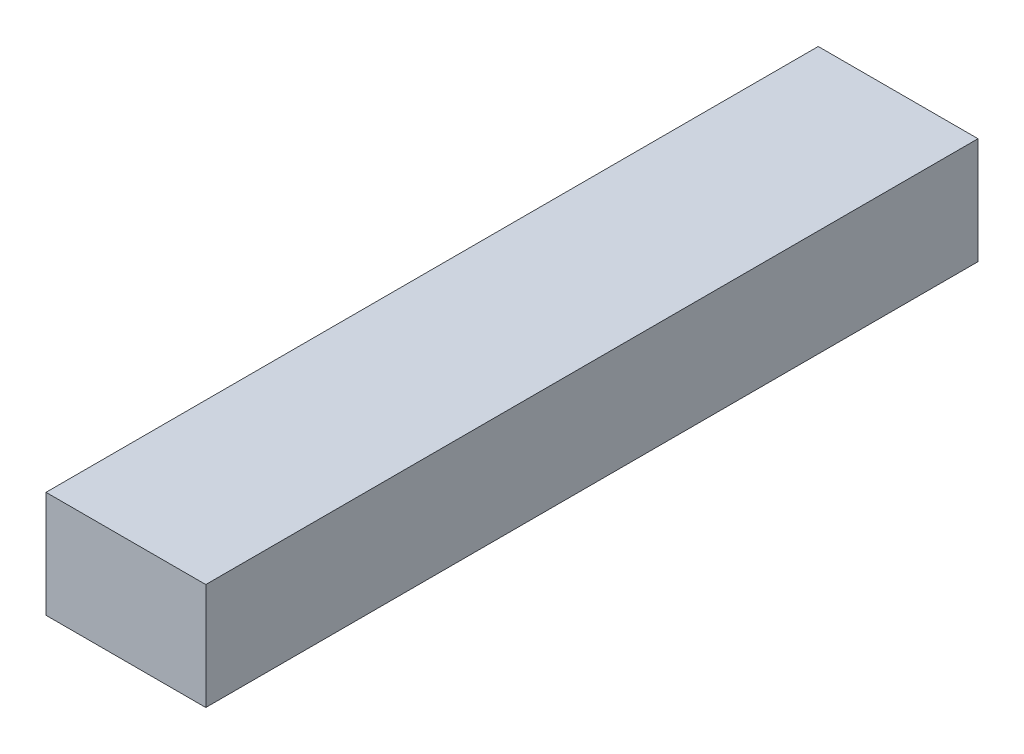
SolidWorks part; units mm, degrees
ref_plane "Front Plane" through (0, 0, 0) normal (0, 0, 1) x (1, 0, 0)
ref_plane "Top Plane" through (0, 0, 0) normal (0, 1, 0) x (1, 0, 0)
ref_plane "Right Plane" through (0, 0, 0) normal (1, 0, 0) x (0, 0, -1)
sketch "Sketch1" plane through (0, 0, 0) normal (0, 1, 0) x (1, 0, 0)
  line L1 (6.6867, 38.2154) -> (36.6867, 38.2154)
  line L2 (6.6867, 38.2154) -> (6.6867, -106.7846)
  line L3 (6.6867, -106.7846) -> (36.6867, -106.7846)
  line L4 (36.6867, 38.2154) -> (36.6867, -106.7846)
  dimension "D1" = 145
  dimension "D2" = 30
extrude "Boss-Extrude1" add sketch "Sketch1" along normal blind 20
